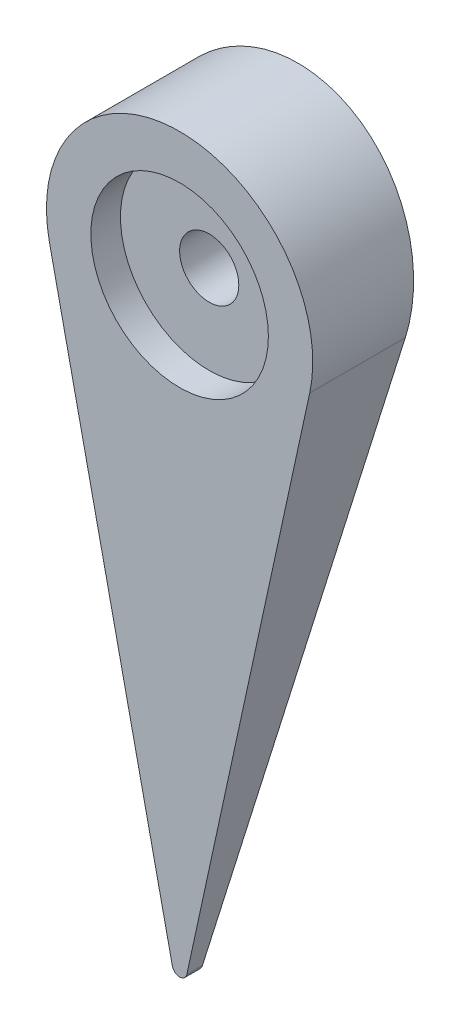
SolidWorks part; units mm, degrees
ref_plane "Plano frontal" through (0, 0, 0) normal (0, 0, 1) x (1, 0, 0)
ref_plane "Plano superior" through (0, 0, 0) normal (0, 1, 0) x (1, 0, 0)
ref_plane "Plano direito" through (0, 0, 0) normal (1, 0, 0) x (0, 0, -1)
sketch "Esboço1" plane through (0, 0, 0) normal (0, 0, 1) x (1, 0, 0)
  line L1 (0, 0) -> (0, -20) construction
  line L2 (4.3972, -0.9562) -> (0.2443, -20.0531)
  line L4 (0, 0) -> (-4.5, 0) construction
  line L5 (0, 0) -> (4.5, 0) construction
  line L6 (-4.3972, -0.9563) -> (-0.2443, -20.0531)
  arc A2 (4.3972, -0.9562) -> (-4.3972, -0.9563) centre (0, 0) ccw
  arc A3 (-0.2443, -20.0531) -> (0.2443, -20.0531) centre (0, -20) ccw
  circle A4 centre (0, 0) radius 1
  dimension "D2" = 0.5
  dimension "D3" = 9
  dimension "D4" = 2
  dimension "D1" = 20
extrude "Ressalto-extrusão1" add sketch "Esboço1" along normal blind 5
sketch "Esboço2" plane through (0, 0, 0) normal (1, 0, 0) x (0, 0, -1)
  line L0 (0, 4.5) -> (0, -20.25)
  line L2 (-5, -20.25) -> (0, -20.25) construction
  line L3 (-4.5, -20.25) -> (0, -20.25)
  line L4 (-4.5, -20.25) -> (-1, 4.5)
  line L5 (-1, 4.5) -> (0, 4.5)
  dimension "D1" = 0.5
  dimension "D2" = 4
extrude "Corte-extrusão1" cut sketch "Esboço2" against normal blind 5 and the other way blind 5
sketch "Esboço3" plane through (0, 0, 5) normal (0, 0, 1) x (1, 0, 0)
  circle A0 centre (0, 0) radius 3
  dimension "D1" = 6
extrude "Corte-extrusão2" cut sketch "Esboço3" against normal blind 1
